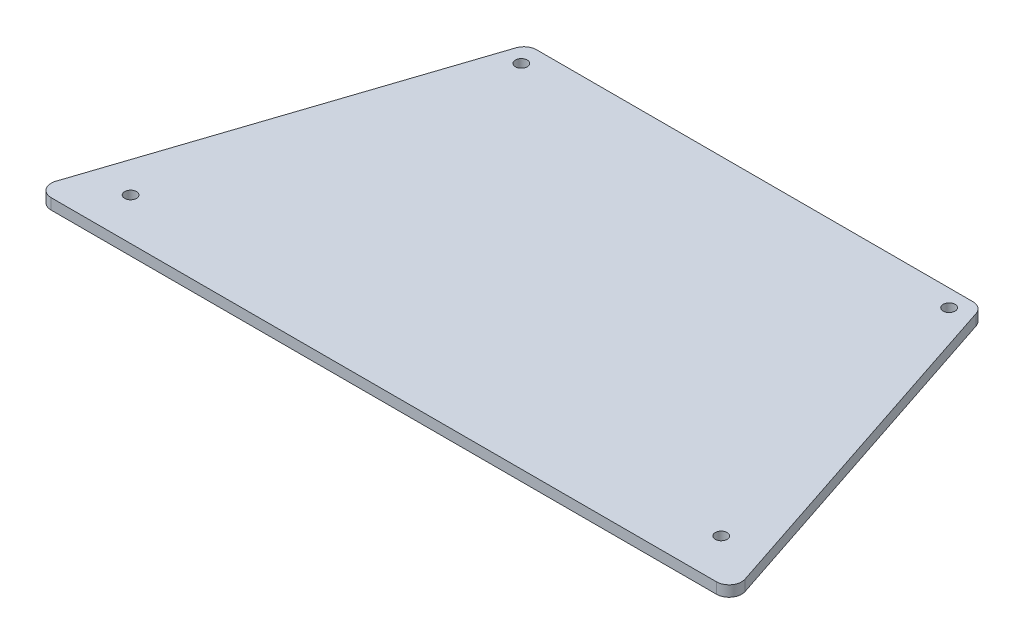
SolidWorks part; units mm, degrees
material "1060 Alloy"
ref_plane "Front Plane" through (0, 0, 0) normal (0, 0, 1) x (1, 0, 0)
ref_plane "Top Plane" through (0, 0, 0) normal (0, 1, 0) x (1, 0, 0)
ref_plane "Right Plane" through (0, 0, 0) normal (1, 0, 0) x (0, 0, -1)
sketch "Sketch1" plane through (0, 0, 0) normal (0, 1, 0) x (1, 0, 0)
  line L0 (-92.375, 0) -> (92.375, 0) construction
  line L1 (96.172, 5.2582) -> (64.367, 101.2357) construction
  line L2 (60.57, 103.9775) -> (-60.57, 103.9775) construction
  line L3 (-64.367, 101.2357) -> (-96.172, 5.2582) construction
  line L4 (-63.8923, 101.0784) -> (-95.6973, 5.101)
  line L5 (-92.375, 0.5) -> (92.375, 0.5)
  line L6 (95.6973, 5.101) -> (63.8923, 101.0784)
  line L7 (60.57, 103.4775) -> (-60.57, 103.4775)
  arc A0 (64.367, 101.2357) -> (60.57, 103.9775) centre (60.57, 99.9775) ccw construction
  arc A1 (-60.57, 103.9775) -> (-64.367, 101.2357) centre (-60.57, 99.9775) ccw construction
  arc A2 (-92.375, 0) -> (-96.172, 5.2582) centre (-92.375, 4) cw construction
  arc A3 (92.375, 0) -> (96.172, 5.2582) centre (92.375, 4) ccw construction
  arc A4 (-92.375, 0.5) -> (-95.6973, 5.101) centre (-92.375, 4) cw
  arc A5 (92.375, 0.5) -> (95.6973, 5.101) centre (92.375, 4) ccw
  arc A6 (63.8923, 101.0784) -> (60.57, 103.4775) centre (60.57, 99.9775) ccw
  arc A7 (-60.57, 103.4775) -> (-63.8923, 101.0784) centre (-60.57, 99.9775) ccw
  point P13 (0, 0)
  dimension "D1" = 4
  dimension "D2" = 184.75
  dimension "D3" = 121.14
  dimension "D4" = 101.11
  dimension "D5" = 0.5
base flange "Base-Flange1" sketch "Sketch1" thickness 3 reverse thickness direction no parameters "D1"=4
edge flange "Edge-Flange1" [suppressed] sketch "Sketch13" flange angle 115 bend radius 4 thickness 3
bend "EdgeBend3" bend radius 4 bend angle 65 parameters "D5"=1
sketch "Sketch13" plane through (0, -3, -103.4775) normal (0, 0.4226, -0.9063) x (1, 0, 0)
  line L0 (58.57, 0) -> (-58.57, 0) construction
  line L1 (-25, 0) -> (25, 0)
  line L2 (25, 0) -> (25, 28.0888)
  line L3 (25, 28.0888) -> (-25, 28.0888)
  line L4 (-25, 28.0888) -> (-25, 0)
  point P8 (0, 0)
  point P9 (0, 0)
  dimension "D1" = 4
  dimension "D6" = 10
  dimension "D7" = 30
edge flange "Edge-Flange3" [suppressed] sketch "Sketch18" flange profiles "Sketch18", "Sketch20" flange angle 98 flange position material inside bend radius 4 thickness 3
sketch "Sketch18" plane through (-85.9494, -3, -28.4819) normal (-0.94, 0.1392, -0.3115) x (0.3146, 0, -0.9492)
  line L0 (76.4787, 0) -> (-24.6313, 0) construction
  line L1 (5.9237, 0) -> (45.9237, 0)
  line L3 (45.9237, 30.3596) -> (5.9237, 30.3596)
  line L5 (5.9237, 0) -> (5.9237, 30.3596)
  line L6 (45.9237, 0) -> (45.9237, 30.3596)
  point P9 (25.9237, 0)
  point P10 (25.9237, 0)
  dimension "D1" = 90
  dimension "D2" = 40
sketch "Sketch20" plane through (85.9494, -3, -28.4819) normal (0.94, 0.1392, -0.3115) x (0.3146, 0, 0.9492)
  line L0 (24.6313, 0) -> (-76.4787, 0) construction
  line L1 (-45.9237, 0) -> (-5.9237, 0)
  line L2 (-45.9237, 32.8556) -> (-45.9237, 0)
  line L3 (-5.9237, 32.8556) -> (-45.9237, 32.8556)
  line L5 (-5.9237, 0) -> (-5.9237, 32.8556)
  point P8 (-25.9237, 0)
  point P9 (-25.9237, 0)
  dimension "D1" = 90
  dimension "D2" = 40
bend "EdgeBend5" bend radius 4 bend angle 82 parameters "D5"=3
bend "EdgeBend7" bend radius 4 bend angle 82 parameters "D5"=3, "D6"=10, "D7"=30.123
fillet "Fillet1" [suppressed] radius 5
sketch "Sketch22" [suppressed] plane through (0, 39.6342, -84.9957) normal (0, 0.4226, -0.9063) x (-1, 0, 0)
  line L0 (-15, -60.9612) -> (15, -60.9612) construction
  line L1 (25, -48.191) -> (-25, -48.191) construction
  line L2 (0, -48.191) -> (0, -73.7315) construction
  line L3 (-20, -73.7315) -> (20, -73.7315) construction
  circle A0 centre (-15, -60.9612) radius 1.55
  circle A1 centre (15, -60.9612) radius 1.55
  point P4 (0, -60.9612)
  point P11 (0, -60.9612)
  dimension "D2" = 3.1
  dimension "D1" = 30
extrude "Cut-Extrude2" [suppressed] cut sketch "Sketch22" against normal up to next
sketch "Sketch23" plane through (0, -3, 0) normal (0, -1, 0) x (1, 0, 0)
  circle A0 centre (-82, -12.1824) radius 1.65
  circle A1 centre (82, -12.1824) radius 1.65
  circle A2 centre (58.7578, -98.7198) radius 1.65
  circle A3 centre (-59.3927, -98.0766) radius 1.65
  dimension "D1" = 3.3
  dimension "D2" = 3.3
  dimension "D3" = 3.3
  dimension "D4" = 3.3
extrude "Cut-Extrude3" cut sketch "Sketch23" against normal up to surface (3 mm away) up to face at (0, 0, -52.4611)
sketch "Sketch24" plane through (0, -3, 0) normal (0, -1, 0) x (1, 0, 0)
  line L0 (0, -19.6874) -> (65, -19.6874) construction
  circle A0 centre (65, -19.6874) radius 3.25
  dimension "D2" = 6.5
  dimension "D1" = 65
extrude "Cut-Extrude4" [suppressed] cut sketch "Sketch24" against normal up to surface (3 mm away)
mirror "Mirror1" [suppressed] about plane through (0, 0, 0) normal (1, 0, 0)
sketch "Bend-Lines1" plane through (0, 0, 0) normal (0, 1, 0) x (1, 0, 0)
sketch "Bounding-Box1" plane through (0, 0, 0) normal (0, 1, 0) x (1, 0, 0)
sheet metal parameters "Sheet-Metal1" thickness 3 parameters "D1"=4
flat pattern "Flat-Pattern1"
sketch "Bend-Lines2" plane through (0, 0, 0) normal (0, 1, 0) x (1, 0, 0)
sketch3d "Bounding-Box2"
  line L0 (-34.805, -98.9774, 0) -> (151.945, -98.9775, 0) construction
  line L1 (-34.8049, 3.0001, 0) -> (151.945, 3, 0) construction
  line L2 (-34.805, -98.9774, 0) -> (-34.8049, 3.0001, 0) construction
  line L3 (151.945, -98.9775, 0) -> (151.945, 3, 0) construction
sheet metal parameters "Sheet-Metal2" thickness 3 parameters "D1"=4
flat pattern "Flat-Pattern1"
sketch "Bend-Lines2" plane through (0, 0, 0) normal (0, 1, 0) x (1, 0, 0)
  line L2 (58.57, 100.2388) -> (-58.57, 100.2388) construction
  line L3 (58.57, 100.2388) -> (-58.57, 100.2388) construction
  point P0 (45, 101.2388)
  point P1 (-45, 101.2388)
sketch3d "Bounding-Box2"
  line L0 (-34.805, -98.9773, 0) -> (151.945, -98.9775, 0) construction
  line L1 (-34.8049, 28.3922, 0) -> (151.9451, 28.3921, 0) construction
  line L2 (-34.805, -98.9773, 0) -> (-34.8049, 28.3922, 0) construction
  line L3 (151.945, -98.9775, 0) -> (151.9451, 28.3921, 0) construction
bend of the flat pattern "Flatten-<EdgeBend3>1"
sheet metal parameters "Sheet-Metal5" thickness 3 parameters "D1"=4
flat pattern "Flat-Pattern1"
sketch "Bend-Lines2" plane through (0, 0, 0) normal (0, 1, 0) x (1, 0, 0)
  line L0 (-68.8082, 72.0353) -> (-81.3906, 34.0658) construction
  line L1 (-68.8082, 72.0353) -> (-81.3906, 34.0658) construction
  line L4 (81.3906, 34.0658) -> (68.8082, 72.0353) construction
  line L5 (25, 102.1378) -> (-25, 102.1378) construction
  line L6 (81.3906, 34.0658) -> (68.8082, 72.0353) construction
  line L7 (25, 102.1378) -> (-25, 102.1378) construction
sketch3d "Bounding-Box2"
  line L0 (164.5489, -99.4775, 0) -> (-45.5934, -99.4775, 0) construction
  line L1 (164.5489, 30.8206, 0) -> (-45.5934, 30.8206, 0) construction
  line L2 (164.5489, -99.4775, 0) -> (164.5489, 30.8206, 0) construction
  line L3 (-45.5934, -99.4775, 0) -> (-45.5934, 30.8206, 0) construction
bend of the flat pattern "Flatten-<EdgeBend3>2"
bend of the flat pattern "Flatten-<EdgeBend5>1"
bend of the flat pattern "Flatten-<EdgeBend7>1"
sheet metal parameters "Sheet-Metal8" thickness 3 parameters "D1"=4
flat pattern "Flat-Pattern1"
sketch "Bend-Lines2" plane through (0, 0, 0) normal (0, 1, 0) x (1, 0, 0)
  line L0 (-68.8082, 72.0353) -> (-81.3906, 34.0658) construction
  line L1 (-68.8082, 72.0353) -> (-81.3906, 34.0658) construction
  line L4 (81.3906, 34.0658) -> (68.8082, 72.0353) construction
  line L5 (25, 102.1378) -> (-25, 102.1378) construction
  line L6 (81.3906, 34.0658) -> (68.8082, 72.0353) construction
  line L7 (25, 102.1378) -> (-25, 102.1378) construction
sketch3d "Bounding-Box2"
  line L0 (-44.8452, -99.4775, 0) -> (163.8006, -99.4775, 0) construction
  line L1 (-44.8452, 30.8206, 0) -> (163.8006, 30.8206, 0) construction
  line L2 (-44.8452, -99.4775, 0) -> (-44.8452, 30.8206, 0) construction
  line L3 (163.8006, -99.4775, 0) -> (163.8006, 30.8206, 0) construction
bend of the flat pattern "Flatten-<EdgeBend3>2"
bend of the flat pattern "Flatten-<EdgeBend5>1"
bend of the flat pattern "Flatten-<EdgeBend7>1"
sheet metal parameters "Sheet-Metal10" thickness 3 parameters "D1"=4
flat pattern "Flat-Pattern1"
sketch "Bend-Lines2" plane through (0, 0, 0) normal (0, 1, 0) x (1, 0, 0)
sketch3d "Bounding-Box2"
  line L0 (-35.305, -99.4773, 0) -> (156.445, -99.4775, 0) construction
  line L1 (-35.3049, 3.5001, 0) -> (156.4451, 3.5, 0) construction
  line L2 (-35.305, -99.4773, 0) -> (-35.3049, 3.5001, 0) construction
  line L3 (156.445, -99.4775, 0) -> (156.4451, 3.5, 0) construction
sheet metal parameters "Sheet-Metal11" thickness 3 parameters "D1"=4
flat pattern "Flat-Pattern1"
sketch "Bend-Lines2" plane through (0, 0, 0) normal (0, 1, 0) x (1, 0, 0)
sketch3d "Bounding-Box2"
  line L0 (-34.805, -98.9774, 0) -> (151.945, -98.9775, 0) construction
  line L1 (-34.8049, 3.0001, 0) -> (151.945, 3, 0) construction
  line L2 (-34.805, -98.9774, 0) -> (-34.8049, 3.0001, 0) construction
  line L3 (151.945, -98.9775, 0) -> (151.945, 3, 0) construction
sheet metal parameters "Sheet-Metal12" thickness 3 parameters "D1"=4
flat pattern "Flat-Pattern1"
sketch "Bend-Lines2" plane through (0, 0, 0) normal (0, 1, 0) x (1, 0, 0)
sketch3d "Bounding-Box2"
  line L0 (-34.805, -98.9774, 0) -> (151.945, -98.9775, 0) construction
  line L1 (-34.8049, 3.0001, 0) -> (151.945, 3, 0) construction
  line L2 (-34.805, -98.9774, 0) -> (-34.8049, 3.0001, 0) construction
  line L3 (151.945, -98.9775, 0) -> (151.945, 3, 0) construction
